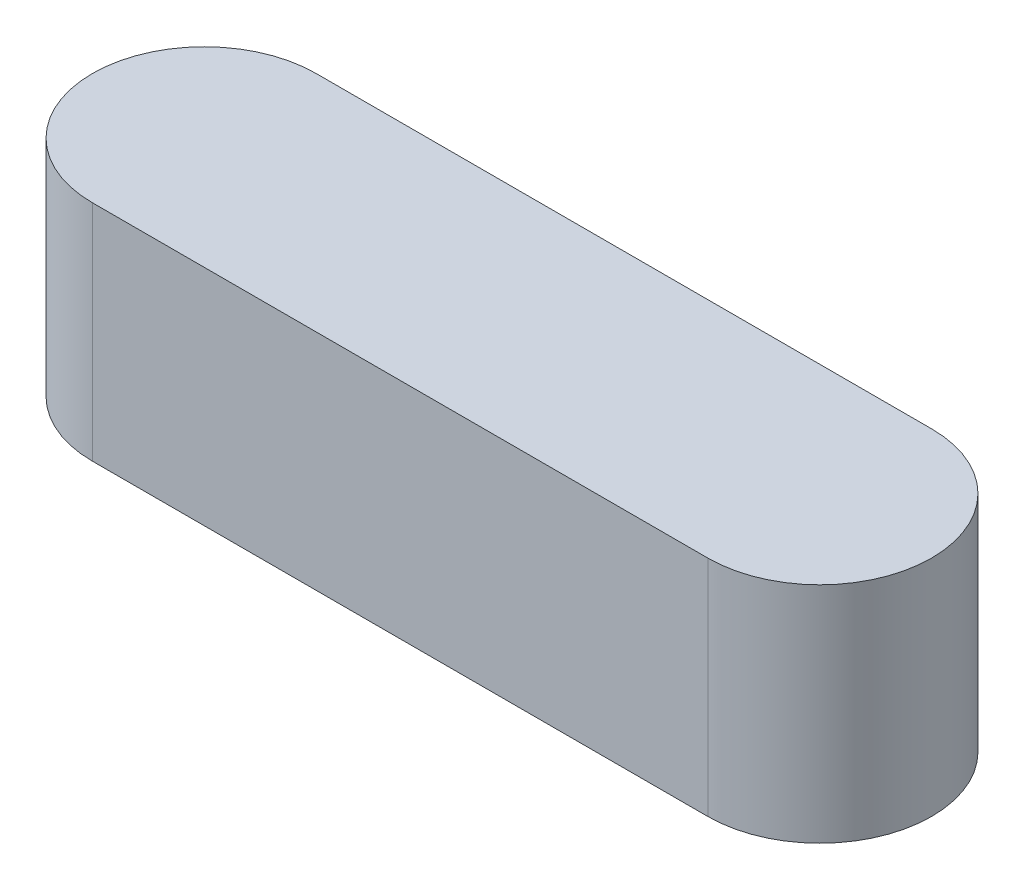
SolidWorks part; units mm, degrees
ref_plane "Front Plane" through (0, 0, 0) normal (0, 0, 1) x (1, 0, 0)
ref_plane "Top Plane" through (0, 0, 0) normal (0, 1, 0) x (1, 0, 0)
ref_plane "Right Plane" through (0, 0, 0) normal (1, 0, 0) x (0, 0, -1)
sketch "Sketch1" plane through (0, 0, 0) normal (0, 1, 0) x (1, 0, 0)
  line L0 (-27.5, 0) -> (27.5, 0) construction
  line L1 (-27.5, 10) -> (27.5, 10)
  line L2 (-27.5, -10) -> (27.5, -10)
  arc A0 (-27.5, 10) -> (-27.5, -10) centre (-27.5, 0) ccw
  arc A1 (27.5, -10) -> (27.5, 10) centre (27.5, 0) ccw
  point P3 (0, 0)
  dimension "D1" = 10
  dimension "D2" = 55
extrude "Boss-Extrude1" add sketch "Sketch1" along normal blind 20
equation "\"TibiaLength\"= 55mm"
equation "\"TibiaRadius\"= 10mm"
equation "\"TibiaThickness\"= 20mm"
equation "\"D1@Sketch1\"= \"TibiaRadius\""
equation "\"D2@Sketch1\" = \"TibiaLength\""
equation "\"D1@Boss-Extrude1\"= \"TibiaThickness\""
